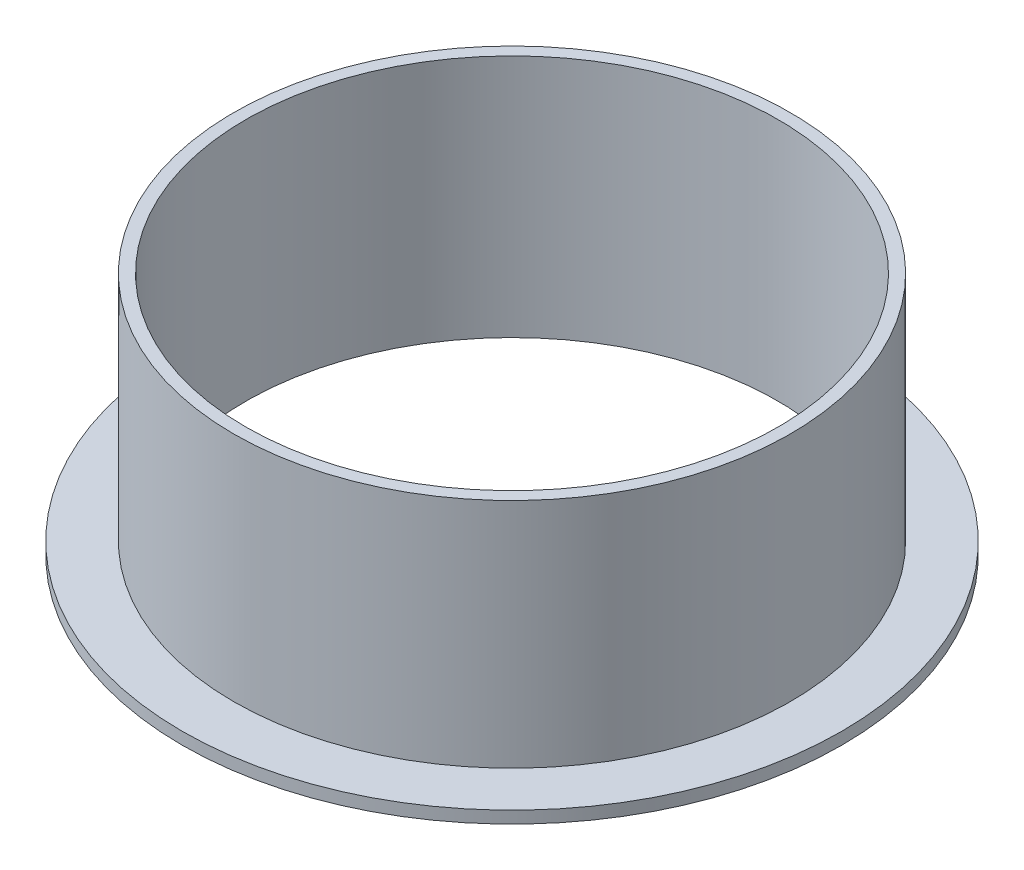
SolidWorks part; units mm, degrees
ref_plane "Front Plane" through (0, 0, 0) normal (0, 0, 1) x (1, 0, 0)
ref_plane "Top Plane" through (0, 0, 0) normal (0, 1, 0) x (1, 0, 0)
ref_plane "Right Plane" through (0, 0, 0) normal (1, 0, 0) x (0, 0, -1)
sketch "Sketch1" plane through (0, 0, 0) normal (0, 1, 0) x (1, 0, 0)
  circle A0 centre (0, 0) radius 69.85
  circle A1 centre (0, 0) radius 86.5
  circle A2 centre (0, 0) radius 73.025
  dimension "5.75in" = 139.7
  dimension "D2" = 146.05
  dimension "D3" = 173
extrude "Boss-Extrude1" add sketch "Sketch1" along normal blind 64 contours A2 A0 region at (-70.9595, 0, 0)
extrude "Boss-Extrude2" add sketch "Sketch1<3>" along normal blind 3.175 contours A1 A2 region at (-84.0534, 0, 0)
sketch "Sketch1<3>" plane through (0, 0, 0) normal (0, 1, 0) x (1, 0, 0) same geometry as "Sketch1"
equation "\"Tube_ID\"= 5.5in"
equation "\"Tube_OD\"= 5.75in"
equation "\"Flange_OD\"= 6in + 13 / 16in"
